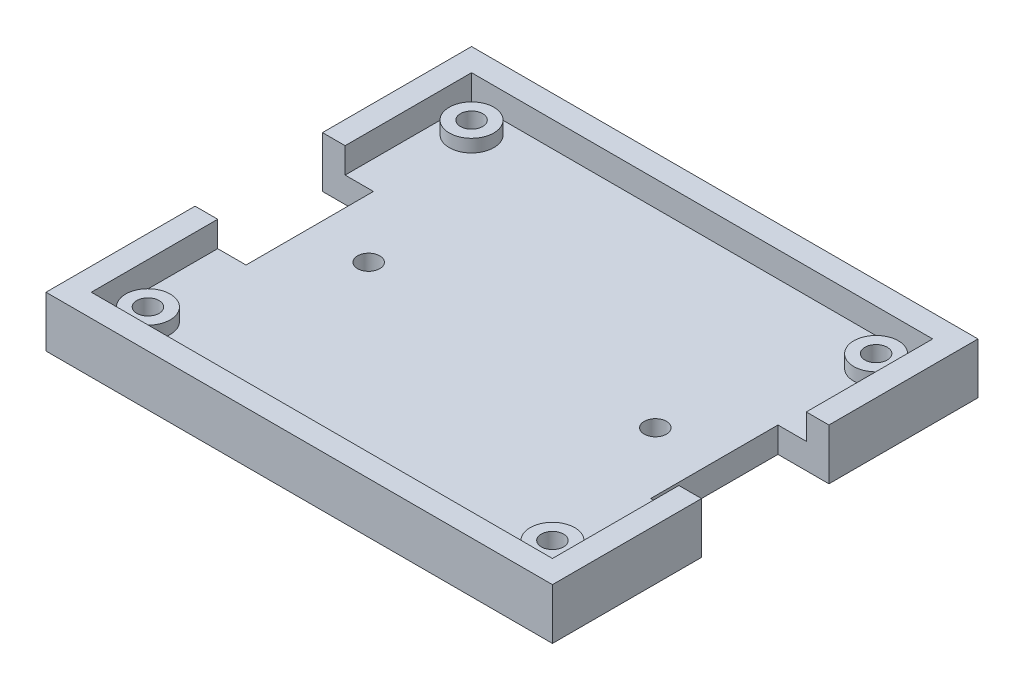
SolidWorks part; units mm, degrees
ref_plane "Front Plane" through (0, 0, 0) normal (0, 0, 1) x (1, 0, 0)
ref_plane "Top Plane" through (0, 0, 0) normal (0, 1, 0) x (1, 0, 0)
ref_plane "Right Plane" through (0, 0, 0) normal (1, 0, 0) x (0, 0, -1)
sketch "Sketch1" plane through (0, 0, 0) normal (0, 1, 0) x (1, 0, 0)
  line L0 (39.75, 0) -> (-39.75, 0)
  line L1 (-31.75, -25.4) -> (31.75, -25.4)
  line L2 (-31.75, -25.4) -> (-31.75, 25.4)
  line L3 (-31.75, 25.4) -> (31.75, 25.4)
  line L4 (31.75, -25.4) -> (31.75, 25.4)
  line L5 (-31.75, -25.4) -> (31.75, 25.4) construction
  line L6 (-31.75, 25.4) -> (31.75, -25.4) construction
  line L7 (-39.75, -33.4) -> (39.75, -33.4)
  line L8 (-39.75, -33.4) -> (-39.75, 33.4)
  line L9 (-39.75, 33.4) -> (39.75, 33.4)
  line L10 (39.75, -33.4) -> (39.75, 33.4)
  line L11 (-39.75, -33.4) -> (39.75, 33.4) construction
  line L12 (-39.75, 33.4) -> (39.75, -33.4) construction
  line L13 (-39.75, -10) -> (39.75, -10)
  line L14 (-39.75, -10) -> (-39.75, 10)
  line L15 (-39.75, 10) -> (39.75, 10)
  line L16 (39.75, -10) -> (39.75, 10)
  line L17 (-39.75, -10) -> (39.75, 10) construction
  line L18 (-39.75, 10) -> (39.75, -10) construction
  line L19 (-36.195, -29.845) -> (36.195, -29.845)
  line L20 (-36.195, -29.845) -> (-36.195, 29.845)
  line L21 (-36.195, 29.845) -> (36.195, 29.845)
  line L22 (36.195, -29.845) -> (36.195, 29.845)
  line L23 (-36.195, -29.845) -> (36.195, 29.845) construction
  line L24 (-36.195, 29.845) -> (36.195, -29.845) construction
  circle A0 centre (-31.75, 25.4) radius 1.75
  circle A1 centre (-31.75, -25.4) radius 1.75
  circle A2 centre (31.75, 25.4) radius 1.75
  circle A3 centre (31.75, -25.4) radius 1.75
  circle A4 centre (-31.75, 25.4) radius 3.5
  circle A5 centre (31.75, 25.4) radius 3.5
  circle A6 centre (31.75, -25.4) radius 3.5
  circle A7 centre (-31.75, -25.4) radius 3.5
  circle A8 centre (22.5, 0) radius 1.75
  circle A9 centre (-22.5, 0) radius 1.75
  point P0 (0, 0)
  point P14 (0, 0)
  point P19 (0, 0)
  point P24 (0, 0)
  dimension "D3" = 3.5
  dimension "D4" = 3.5
  dimension "D5" = 3.5
  dimension "D6" = 3.5
  dimension "D7" = 7
  dimension "D8" = 7
  dimension "D9" = 7
  dimension "D18" = 3.5
  dimension "D19" = 3.5
  dimension "D20" = 7
  dimension "D1" = 63.5
  dimension "D2" = 50.8
  dimension "D10" = 8
  dimension "D11" = 8
  dimension "D12" = 20
  dimension "D13" = 72.39
  dimension "D14" = 59.69
  dimension "D15" = 3.555
  dimension "D16" = 22.5
  dimension "D17" = 22.5
extrude "Boss-Extrude1" add sketch "Sketch1" along normal blind 4 contours A9 L0 L2 L13 L4 A8 | A9 L0 A8 L4 L15 L2 | A7 L1 A6 L4 L13 L2 | A5 L3 A4 L2 L15 L4 | A7 L2 L13 L20 L19 L22 L4 A6 L1 | A5 L4 L15 L22 L21 L20 L2 A4 L3 region at (0, 0, 5.0655) region at (0, 0, -5.0655) region at (35.4444, 0, 19.9225) region at (33.9725, 0, -10.7506) region at (0, 0, 17.5753) region at (0, 0, -17.5753)
extrude "Boss-Extrude2" add sketch "Sketch1<3>" along normal blind 8 contours L22 L19 L20 L13 L8 L7 L10 | L22 L15 L10 L9 L8 L20 L21 region at (38.9213, 0, 21.7) region at (37.9725, 0, -10.8287)
sketch "Sketch1<3>" plane through (0, 0, 0) normal (0, 1, 0) x (1, 0, 0) same geometry as "Sketch1"
extrude "Boss-Extrude3" add sketch "Sketch1<4>" along normal blind 6 contours L1 A6 L4 A3 | L4 A6 L1 A3 | L1 A7 L2 A1 | L2 A7 L1 A1 | L3 A4 L2 A0 | L2 A4 L3 A0 | L4 A5 L3 A2 | L3 A5 L4 A2 region at (34.1549, 0, 22.9951) region at (30.017, 0, 23.667) region at (30.017, 0, -23.667) region at (31.849, 0, -22.775) region at (-30.017, 0, 23.667) region at (-31.849, 0, 22.775) region at (-34.1549, 0, -27.8049) region at (-30.017, 0, -23.667)
sketch "Sketch1<4>" plane through (0, 0, 0) normal (0, 1, 0) x (1, 0, 0) same geometry as "Sketch1"
